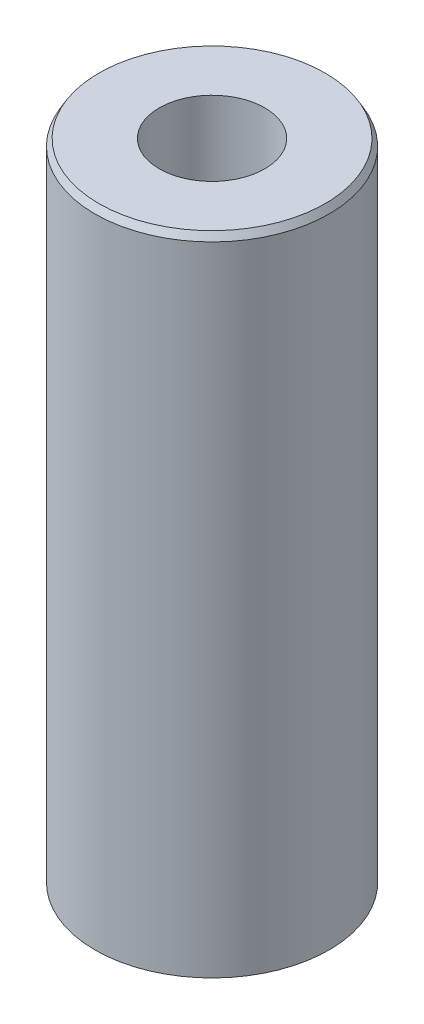
SolidWorks part; units mm, degrees
ref_plane "Front Plane" through (0, 0, 0) normal (0, 0, 1) x (1, 0, 0)
ref_plane "Top Plane" through (0, 0, 0) normal (0, 1, 0) x (1, 0, 0)
ref_plane "Right Plane" through (0, 0, 0) normal (1, 0, 0) x (0, 0, -1)
sketch "Sketch1" plane through (0, 0, 0) normal (0, 1, 0) x (1, 0, 0)
  circle A0 centre (0, 0) radius 57.5
  dimension "SHAFT_OD" = 115
extrude "Boss-Extrude1" add sketch "Sketch1" along normal blind 318.2979
sketch "Sketch2" plane through (0, 0, 0) normal (0, 1, 0) x (1, 0, 0)
  circle A0 centre (0, 0) radius 25.9283
  dimension "BORE_D" = 51.8567
extrude "Cut-Extrude1" cut sketch "Sketch2" along normal through all
chamfer "Chamfer1" distance 3.4025 angle 30 2 edges at (0, 318.2979, 57.5) (0, 0, 57.5) first distance on face at (0, 318.2979, 57.5) first distance on face at (0, 0, 25.9283)
